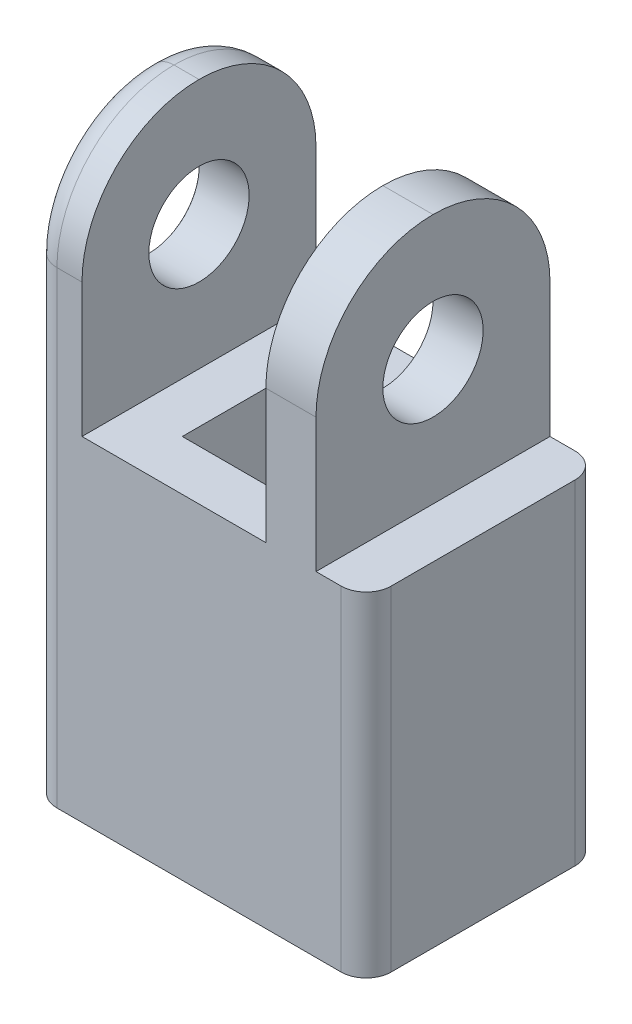
SolidWorks part; units mm, degrees
ref_plane "Front Plane" through (0, 0, 0) normal (0, 0, 1) x (1, 0, 0)
ref_plane "Top Plane" through (0, 0, 0) normal (0, 1, 0) x (1, 0, 0)
ref_plane "Right Plane" through (0, 0, 0) normal (1, 0, 0) x (0, 0, -1)
sketch "Sketch2" plane through (0, 0, 0) normal (0, 1, 0) x (1, 0, 0)
  line L1 (0, 0) -> (40, 0)
  line L2 (0, 0) -> (0, 28)
  line L3 (0, 28) -> (40, 28)
  line L4 (40, 0) -> (40, 28)
  dimension "D1" = 40
  dimension "D2" = 28
extrude "Boss-Extrude2" add sketch "Sketch2" along normal blind 40
sketch "Sketch3" plane through (0, 40, 0) normal (0, 1, 0) x (1, 0, 0)
  line L0 (0, 0) -> (40, 0) construction
  line L1 (0, 28) -> (6, 28)
  line L2 (0, 28) -> (0, 0)
  line L3 (0, 0) -> (6, 0)
  line L4 (6, 28) -> (6, 0)
  line L5 (40, 28) -> (0, 28) construction
  line L6 (28, 28) -> (34, 28)
  line L7 (28, 28) -> (28, 0)
  line L8 (28, 0) -> (34, 0)
  line L9 (34, 28) -> (34, 0)
  dimension "D1" = 6
  dimension "D2" = 22
  dimension "D3" = 6
extrude "Boss-Extrude3" add sketch "Sketch3" along normal blind 30
hole_wizard "Ø12.0mm Dowel Hole1" positions "3DSketch1" profile "Sketch4" hole size "Ø12.0" standard "ANSI Metric" end condition through all
sketch3d "3DSketch1"
  line L0 (0, 70, 0) -> (0, 0, 0) construction
  line L2 (0, 70, -28) -> (0, 70, 0) construction
  point P0 (0, 55, -14)
  dimension "D1" = 14
  dimension "D2" = 15
sketch "Sketch4" plane through (0, 55, -14) normal (0, 1, 0) x (0, 0, 1)
  line L0 (0, 0) -> (0, 40)
  line L1 (0, 40) -> (6, 40)
  line L2 (6, 40) -> (6, 0.025)
  line L3 (6, 0.025) -> (6.025, 0)
  line L5 (6.025, 0) -> (0, 0)
  line L6 (-6, 0.025) -> (-6.025, 0) construction
  line L11 (0, -6.35) -> (0, 107.95) construction
  dimension "Thru Hole Dia." = 12
  dimension "Thru Hole Depth" = 40
  dimension "Near C'Sink Dia." = 12.05
  dimension "Near C'Sink Angle" = 90
fillet "Fillet5" radius 14 1 edges at (3, 70, 0)
fillet "Fillet3" radius 14 1 edges at (31, 70, -28)
fillet "Fillet4" radius 14 1 edges at (31, 70, 0)
fillet "Fillet6" radius 14 1 edges at (3, 70, -28)
fillet "Fillet7" radius 3 4 edges at (0, 65.8995, -4.1005) (0, 65.8995, -23.8995) (0, 28, 0) (0, 28, -28)
fillet "Fillet8" radius 3 2 edges at (40, 20, -28) (40, 20, 0)
sketch "Sketch5" plane through (0, 40, 0) normal (0, 1, 0) x (1, 0, 0)
  line L0 (28, 28) -> (28, 0) construction
  line L1 (12, 22) -> (28, 22)
  line L2 (12, 22) -> (12, 6)
  line L3 (12, 6) -> (28, 6)
  line L4 (28, 22) -> (28, 6)
  line L5 (28, 28) -> (6, 28) construction
  line L6 (6, 0) -> (28, 0) construction
  line L7 (6, 0) -> (6, 28) construction
  dimension "D1" = 6
  dimension "D2" = 6
  dimension "D3" = 6
extrude "Cut-Extrude1" cut sketch "Sketch5" against normal through all
